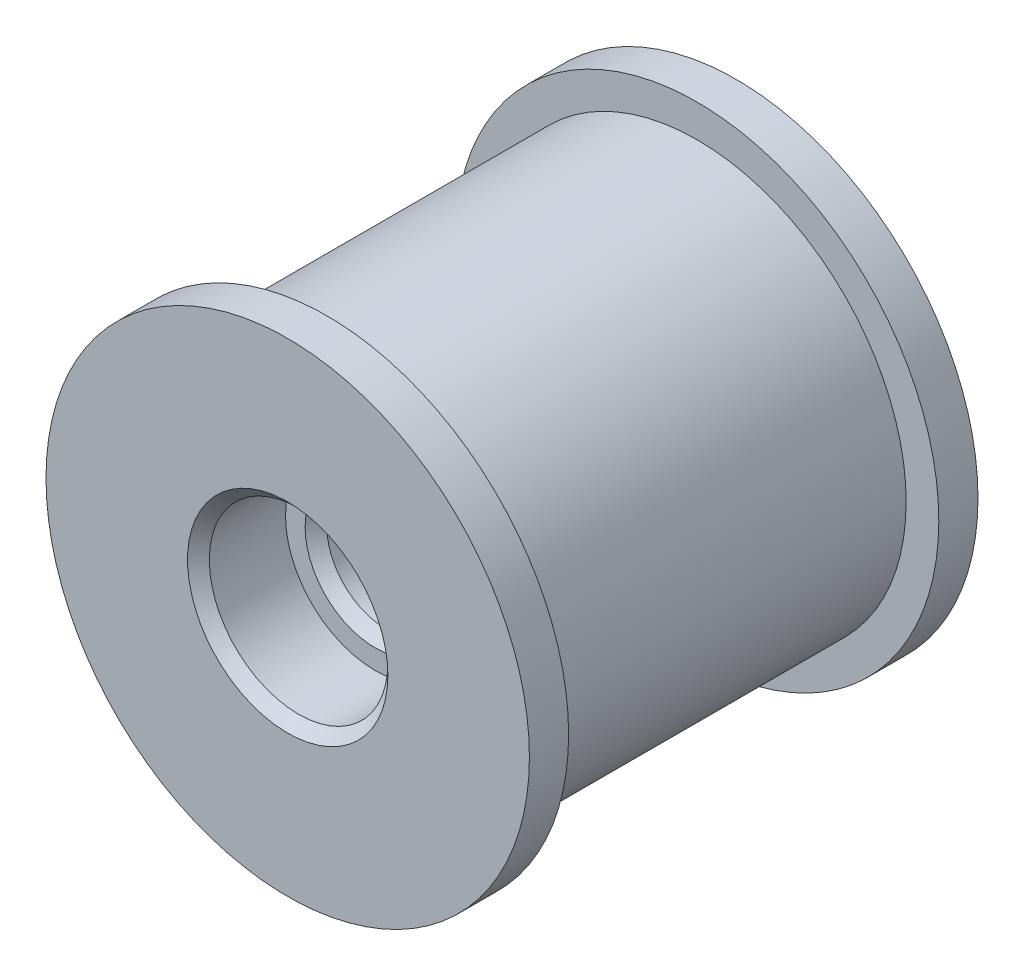
SolidWorks part; units mm, degrees
ref_plane "Ebene vorne" through (0, 0, 0) normal (0, 0, 1) x (1, 0, 0)
ref_plane "Ebene oben" through (0, 0, 0) normal (0, 1, 0) x (1, 0, 0)
ref_plane "Ebene rechts" through (0, 0, 0) normal (1, 0, 0) x (0, 0, -1)
sketch "Skizze1" plane through (0, 0, 0) normal (0, 0, 1) x (1, 0, 0)
  circle A0 centre (0, 0) radius 9.6
  dimension "D1" = 19.2
extrude "Aufsatz-Linear austragen1" add sketch "Skizze1" along normal blind 10.3 and the other way blind 10.3
ref_axis "Rotationsachse" [suppressed] through (0, 0, -9.8) along (0, 0, 1)
sketch "Skizze2" plane through (0, 0, 10.3) normal (0, 0, 1) x (1, 0, 0)
  circle A0 centre (0, 0) radius 11.1
  dimension "D1" = 22.2
extrude "Aufsatz-Linear austragen2" add sketch "Skizze2" against normal blind 1.8
sketch "Skizze3" plane through (0, 0, -10.3) normal (0, 0, -1) x (-1, 0, 0)
  circle A0 centre (0, 0) radius 11.1
  dimension "D1" = 22.2
extrude "Aufsatz-Linear austragen3" add sketch "Skizze3" against normal blind 1.8
sketch "Skizze8" plane through (0, 0, 0) normal (1, 0, 0) x (0, 0, -1)
  line L0 (10.3, 0) -> (10.3, 8)
  line L1 (10.3, -11.1) -> (10.3, 11.1) construction
  line L2 (10.3, 8) -> (8.5, 8)
  line L3 (8.5, 11.1) -> (8.5, -11.1) construction
  line L8 (8.5, 8) -> (-3.7, 4)
  line L9 (-3.7, 4) -> (-3.7, 2.7)
  line L10 (-3.7, 2.7) -> (-6.3, 2.7)
  line L11 (-6.3, 2.7) -> (-6.3, 4.1)
  line L12 (-6.3, 4.1) -> (-10.3, 4.1)
  line L13 (-10.3, 11.1) -> (-10.3, -11.1) construction
  line L14 (-10.3, 4.1) -> (-10.3, 0)
  line L15 (-10.3, 0) -> (10.3, 0)
  dimension "D1" = 8
  dimension "D2" = 4
  dimension "D3" = 4.1
  dimension "D4" = 14
  dimension "D5" = 4
  dimension "D6" = 2.7
revolve "Schnitt-Rotation1" cut sketch "Skizze8" angle 360 about axis through (0, 0, -9.8) along (0, 0, 1)
chamfer "Fase1" distance 0.5 3 edges at (-2.7, 0, 6.3) (-2.7, 0, 3.7) (-4.1, 0, 10.3)
